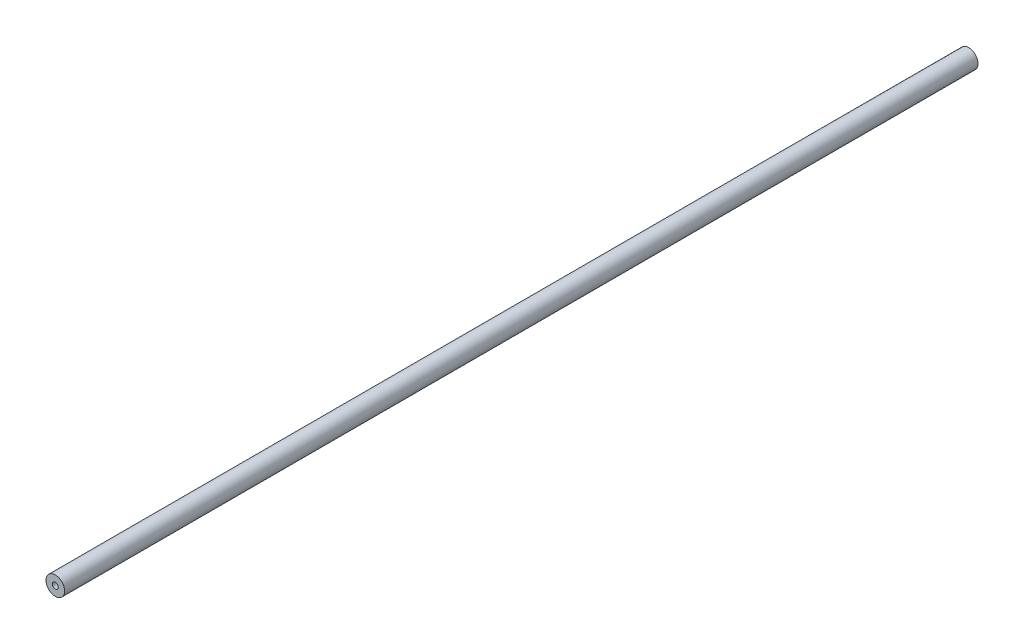
SolidWorks part; units mm, degrees
material "6061-T6 (SS)"
ref_plane "Front Plane" through (0, 0, 0) normal (0, 0, 1) x (1, 0, 0)
ref_plane "Top Plane" through (0, 0, 0) normal (0, 1, 0) x (1, 0, 0)
ref_plane "Right Plane" through (0, 0, 0) normal (1, 0, 0) x (0, 0, -1)
sketch "Sketch1" plane through (0, 0, 0) normal (0, 0, 1) x (1, 0, 0)
  circle A0 centre (0, 0) radius 6.35
  dimension "D1" = 12.7
extrude "Boss-Extrude1" add sketch "Sketch1" along normal blind 622.554
hole_wizard "#10-32 Tapped Hole1" positions "Sketch3" profile "Sketch2" tap size "#10-32" standard "ANSI Inch"
sketch "Sketch3" plane through (0, 0, 622.554) normal (0, 0, 1) x (1, 0, 0)
  point P0 (0, 0)
sketch "Sketch2" plane through (0, 0, 622.554) normal (1, 0, 0) x (0, -1, 0)
  line L0 (0, 0) -> (0, 14.9293)
  line L1 (0, 14.9293) -> (2.0193, 13.716)
  line L2 (2.0193, 13.716) -> (2.0193, 0)
  line L5 (2.0193, 0) -> (0, 0)
  line L10 (0, 14.9293) -> (-2.0193, 13.716) construction
  line L11 (0, -6.35) -> (0, 107.95) construction
  dimension "Tap Drill Dia." = 4.0386
  dimension "Tap Drill Depth" = 13.716
  dimension "Drill Angle" = 118
cosmetic thread "Hole Thread1"
hole_wizard "#10-32 Tapped Hole2" positions "Sketch5" profile "Sketch4" tap size "#10-32" standard "ANSI Inch"
sketch "Sketch5" plane through (0, 0, 0) normal (0, 0, -1) x (-1, 0, 0)
  point P0 (0, 0)
sketch "Sketch4" plane through (0, 0, 0) normal (1, 0, 0) x (0, 1, 0)
  line L0 (0, 0) -> (0, 14.9293)
  line L1 (0, 14.9293) -> (2.0193, 13.716)
  line L2 (2.0193, 13.716) -> (2.0193, 0)
  line L5 (2.0193, 0) -> (0, 0)
  line L10 (0, 14.9293) -> (-2.0193, 13.716) construction
  line L11 (0, -6.35) -> (0, 107.95) construction
  dimension "Tap Drill Dia." = 4.0386
  dimension "Tap Drill Depth" = 13.716
  dimension "Drill Angle" = 118
cosmetic thread "Hole Thread2" parameters "D1"=9.652, "D2"=4.826
